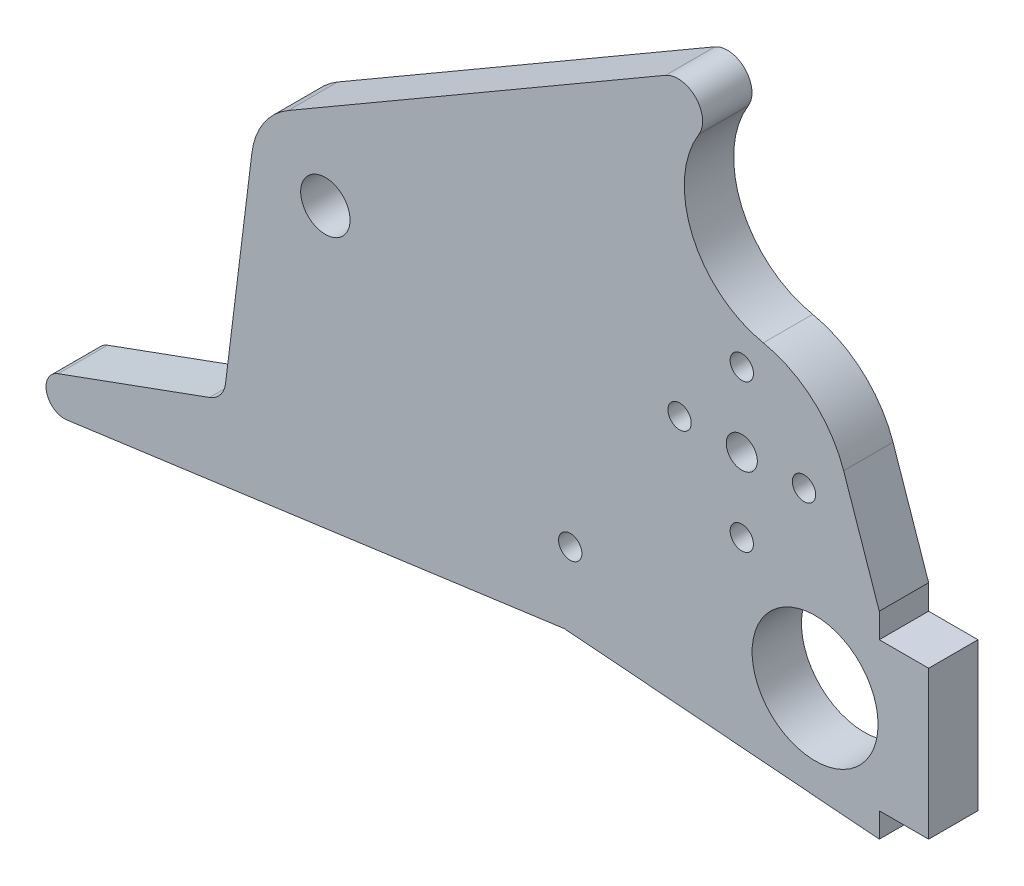
SolidWorks part; units mm, degrees
ref_plane "Front Plane" through (0, 0, 0) normal (0, 0, 1) x (1, 0, 0)
ref_plane "Top Plane" through (0, 0, 0) normal (0, 1, 0) x (1, 0, 0)
ref_plane "Right Plane" through (0, 0, 0) normal (1, 0, 0) x (0, 0, -1)
sketch "Sketch1" plane through (0, 0, 0) normal (0, 0, 1) x (1, 0, 0)
  line L0 (12.2605, 58.6546) -> (-36.2799, 30.4615)
  line L1 (0, -55) -> (0, 55) construction
  line L2 (39.751, 9.525) -> (46.101, 9.525)
  line L3 (39.751, 9.525) -> (39.751, -9.525) construction
  line L4 (39.751, -9.525) -> (46.101, -9.525)
  line L5 (46.101, 9.525) -> (46.101, -9.525)
  line L6 (14.0686, 21.567) -> (30.0686, 21.567) construction
  line L7 (22.0686, 31.067) -> (22.0686, 12.067) construction
  line L8 (39.751, 9.525) -> (39.751, 12.7)
  line L9 (39.751, -9.525) -> (39.751, -12.7)
  line L10 (-36.9877, 14.4425) -> (-5.4917, -7.7825)
  line L11 (39.751, -12.7) -> (-0.7513, -9.4953)
  line L12 (-18.0656, 110.4417) -> (26016.8979, -39640.6484) construction
  line L14 (22.0686, 21.567) -> (34.7171, 29.8512) construction
  line L15 (39.751, 12.7) -> (35.1696, 26.0597)
  line L16 (22.0686, 21.567) -> (23.8659, 17.4552)
  line L17 (23.8659, 17.4552) -> (27.6159, 8.8765) construction
  line L18 (27.6159, 8.8765) -> (28.2517, 7.4219)
  line L19 (28.2517, 7.4219) -> (31.496, 0) construction
  circle A2 centre (31.496, 0) radius 19.05 construction
  circle A3 centre (-31.496, 0) radius 19.05 construction
  circle A4 centre (-31.496, 22.225) radius 38.1 construction
  circle A5 centre (0, 0) radius 1.5
  circle A6 centre (22.0686, 31.067) radius 1.5
  circle A7 centre (30.0686, 21.567) radius 1.5
  circle A8 centre (22.0686, 12.067) radius 1.5
  circle A9 centre (14.0686, 21.567) radius 1.5
  circle A11 centre (-31.496, 22.225) radius 3.175
  arc A12 (-36.2799, 30.4615) -> (-36.9877, 14.4425) centre (-31.496, 22.225) ccw
  arc A19 (35.1696, 26.0597) -> (24.8346, 35.138) centre (22.0686, 21.567) ccw
  arc A20 (16.5583, 54.2437) -> (12.2605, 58.6546) centre (13.8552, 55.9091) ccw
  arc A21 (-5.4917, -7.7825) -> (-0.7513, -9.4953) centre (0, 0) ccw
  arc A22 (16.5583, 54.2437) -> (24.8346, 35.138) centre (27.371, 47.5822) ccw
  arc A23 (-36.9877, 14.4425) -> (-36.2799, 30.4615) centre (-31.496, 22.225) ccw construction
  circle A31 centre (22.0686, 21.567) radius 2
  arc A33 (4.086, 8.6041) -> (-5.4917, -7.7825) centre (0, 0) ccw construction
  arc A34 (-0.7513, -9.4953) -> (4.086, 8.6041) centre (0, 0) ccw construction
  arc A35 (24.8346, 35.138) -> (15.0556, 9.6238) centre (22.0686, 21.567) ccw construction
  arc A36 (15.0556, 9.6238) -> (35.1696, 26.0597) centre (22.0686, 21.567) ccw construction
  circle A37 centre (31.496, 0) radius 8.1
  point P2 (33.6547, 29.1554)
  point P10 (46.101, 0)
  point P13 (-31.496, -19.05)
  point P24 (-31.496, -15.875)
  point P26 (22.0686, 21.567)
  point P29 (22.0686, 21.567)
  point P37 (42.926, -9.525)
  point P53 (-1.667, 57.6548)
  point P54 (22.7076, 51.8193)
  point P55 (0, 0)
  point P57 (-5.6812, 55.2831)
  point P58 (0, 0)
  point P59 (0, 0)
  point P60 (18.6337, 61.83)
  point P61 (0, 0)
  point P62 (11.4623, 59.8759)
  point P63 (11.3575, 58.6248)
  point P64 (14.0686, 56.6695)
  point P65 (13.3747, 56.6428)
  dimension "D7" = 38.1
  dimension "D8" = 76.2
  dimension "D11" = 3
  dimension "D13" = 3
  dimension "D14" = 27.7
  dimension "D16" = 6.35
  dimension "D17" = 19.05
  dimension "D21" = 6.35
  dimension "D22" = 1.5875
  dimension "D23" = 16.2
  dimension "D25" = 56.134
  dimension "D26" = 4
  dimension "D19" = 19.05
  dimension "D24" = 12.7
  dimension "D3" = 19.05
  dimension "D4" = 6.35
  dimension "D5" = 11.43
  dimension "D6" = 62.992
  dimension "D9" = 3.175
  dimension "D10" = 19
  dimension "D12" = 16
  dimension "D15" = 1.27
  dimension "D18" = 53.5686
  dimension "D20" = 3.175
extrude "Boss-Extrude1" add sketch "Sketch1" along normal mid plane 6.35 contours L10 L11 L9 L4 L5 L2 L8 A12 A20 A6 A7 A8 A9 A11 region at (3.5012, 18.9329, 0)
sketch "Sketch2" plane through (0, 0, 3.175) normal (0, 0, 1) x (1, 0, 0)
  line L0 (-46.398, -6.562) -> (-65.8615, -13.6461) construction
  line L1 (-46.398, -6.562) -> (-65.8615, -13.6461)
  line L2 (-44.3329, -3.9682) -> (-40.949, 23.3941)
  line L3 (-64.7244, -18.2431) -> (-0.7513, -9.4953)
  line L4 (-36.9877, 14.4425) -> (-5.4917, -7.7825) construction
  line L5 (-36.9877, 14.4425) -> (-5.4917, -7.7825)
  arc A0 (-65.8615, -13.6461) -> (-64.8428, -18.2563) centre (-65.0471, -15.8838) ccw construction
  arc A1 (-65.8615, -13.6461) -> (-64.7244, -18.2431) centre (-65.0471, -15.8838) ccw
  arc A2 (-5.4917, -7.7825) -> (-0.7513, -9.4953) centre (0, 0) ccw construction
  arc A3 (-46.398, -6.562) -> (-44.3329, -3.9682) centre (-47.4839, -3.5785) ccw
  arc A4 (-36.2799, 30.4615) -> (-36.9877, 14.4425) centre (-31.496, 22.225) ccw construction
  arc A5 (-5.4917, -7.7825) -> (-0.7513, -9.4953) centre (0, 0) ccw
  arc A6 (-40.949, 23.3941) -> (-36.9877, 14.4425) centre (-31.496, 22.225) ccw
  dimension "D1" = 3.175
extrude "Boss-Extrude2" add sketch "Sketch2" against normal up to surface (6.35 mm away) up to face at (39.596, 0, -3.175)
